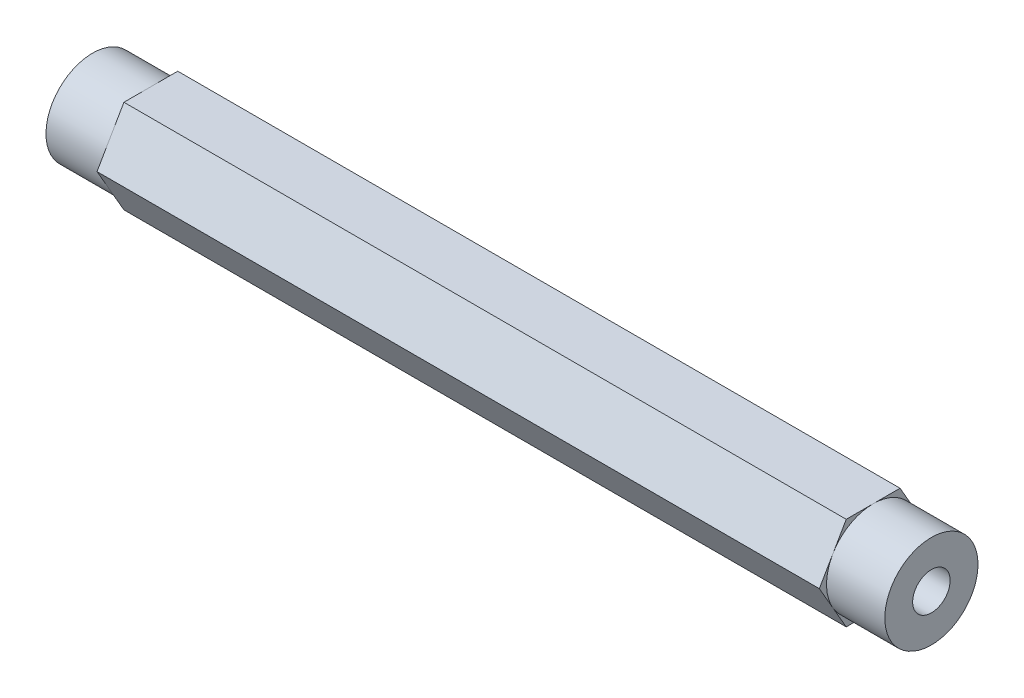
SolidWorks part; units mm, degrees
material "6061-T6 (SS)"
ref_plane "Front Plane" through (0, 0, 0) normal (0, 0, 1) x (1, 0, 0)
ref_plane "Top Plane" through (0, 0, 0) normal (0, 1, 0) x (1, 0, 0)
ref_plane "Right Plane" through (0, 0, 0) normal (1, 0, 0) x (0, 0, -1)
sketch "Sketch2" plane through (0, 0, 0) normal (1, 0, 0) x (0, 0, -1)
  line L1 (7.3323, 0) -> (3.6662, 6.35)
  line L2 (3.6662, 6.35) -> (-3.6662, 6.35)
  line L3 (-3.6662, 6.35) -> (-7.3323, 0)
  line L4 (-7.3323, 0) -> (-3.6662, -6.35)
  line L5 (-3.6662, -6.35) -> (3.6662, -6.35)
  line L6 (3.6662, -6.35) -> (7.3323, 0)
  circle A0 centre (0, 0) radius 6.35 construction
  dimension "D1" = 12.7
extrude "Boss-Extrude1" add sketch "Sketch2" along normal mid plane 114.3
sketch "Sketch3" plane through (57.15, 0, 0) normal (1, 0, 0) x (0, 0, -1)
  circle A0 centre (0, 0) radius 6.35
  dimension "D1" = 12.7
extrude "Cut-Extrude-Thin1" cut sketch "Sketch3" against normal blind 7.9375 thin thin type one direction wall 2.54
mirror "Mirror1" about plane through (0, 0, 0) normal (1, 0, 0) of "Cut-Extrude-Thin1"
hole_wizard "1/4-20 Tapped Hole1" positions "3DSketch1" profile "Sketch5" tap size "1/4-20" standard "ANSI Inch"
sketch3d "3DSketch1"
  line L0 (49.2125, 0, 0) -> (57.15, 0, 0) construction
  line L1 (-49.2125, 0, 0) -> (-57.15, 0, 0) construction
  point P0 (57.15, 0, 0)
  point P4 (-57.15, 0, 0)
sketch "Sketch5" plane through (57.15, 0, 0) normal (0, 1, 0) x (0, 0, -1)
  line L0 (0, 0) -> (0, 18.0438)
  line L1 (0, 18.0438) -> (2.5527, 16.51)
  line L2 (2.5527, 16.51) -> (2.5527, 0)
  line L5 (2.5527, 0) -> (0, 0)
  line L10 (0, 18.0438) -> (-2.5527, 16.51) construction
  line L11 (0, -6.35) -> (0, 107.95) construction
  dimension "Tap Drill Dia." = 5.1054
  dimension "Tap Drill Depth" = 16.51
  dimension "Drill Angle" = 118
cosmetic thread "Hole Thread1" parameters "D1"=12.7, "D2"=6.35
cosmetic thread "Hole Thread2" parameters "D1"=12.7, "D2"=6.35
